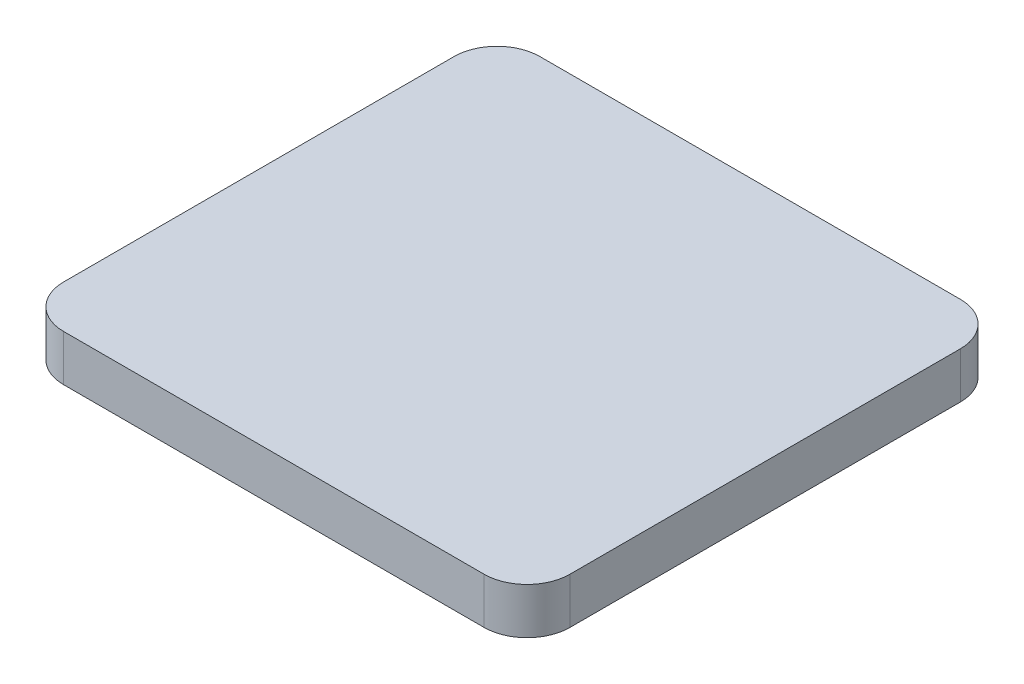
SolidWorks part; units mm, degrees
ref_plane "Front Plane" through (0, 0, 0) normal (0, 0, 1) x (1, 0, 0)
ref_plane "Top Plane" through (0, 0, 0) normal (0, 1, 0) x (1, 0, 0)
ref_plane "Right Plane" through (0, 0, 0) normal (1, 0, 0) x (0, 0, -1)
sketch "Sketch1" plane through (0, 0, 0) normal (0, 1, 0) x (1, 0, 0)
  line L0 (-21.6, 20.2) -> (-21.6, 22.2) construction
  line L1 (19.6, 20.2) -> (-19.6, 20.2)
  line L2 (21.6, 18.2) -> (21.6, -18.2)
  line L3 (19.6, -20.2) -> (-19.6, -20.2)
  line L4 (-21.6, 18.2) -> (-21.6, -18.2)
  line L5 (21.6, 20.2) -> (-21.6, -20.2) construction
  line L6 (21.6, -20.2) -> (-21.6, 20.2) construction
  line L7 (23.6, -22.2) -> (-23.6, -22.2)
  line L8 (23.6, -22.2) -> (23.6, 22.2)
  line L9 (23.6, 22.2) -> (-23.6, 22.2)
  line L10 (-23.6, -22.2) -> (-23.6, 22.2)
  line L11 (23.6, -22.2) -> (-23.6, 22.2) construction
  line L12 (23.6, 22.2) -> (-23.6, -22.2) construction
  line L13 (-21.6, 20.2) -> (-23.6, 20.2) construction
  arc A0 (-19.6, -20.2) -> (-21.6, -18.2) centre (-19.6, -18.2) cw
  arc A1 (21.6, -18.2) -> (19.6, -20.2) centre (19.6, -18.2) cw
  arc A2 (19.6, 20.2) -> (21.6, 18.2) centre (19.6, 18.2) cw
  arc A3 (-19.6, 20.2) -> (-21.6, 18.2) centre (-19.6, 18.2) ccw
  circle A4 centre (-19.6, 18.2) radius 4
  circle A5 centre (19.6, 18.2) radius 4
  circle A6 centre (19.6, -18.2) radius 4
  circle A7 centre (-19.6, -18.2) radius 4
  point P0 (0, 0)
  point P6 (0, 0)
  dimension "D4" = 2
  dimension "D1" = 43.2
  dimension "D2" = 40.4
  dimension "D3" = 2
extrude "Boss-Extrude1" add sketch "Sketch1" along normal blind 1.3 contours L1 A4 L4 A3 | A7 L4 A4 L10 | A7 L3 A0 L4 | A7 L7 A6 L3 | A6 L2 A1 L3 | A6 L8 A5 L2 | L2 A5 L1 A2 | A5 L9 A4 L1 region at (17.8679, 0, -20.3056) region at (0, 0, -21.2258) region at (-17.8679, 0, -20.3056) region at (22.6281, 0, 0) region at (22.9727, 0, 16.2528) region at (-22.6281, 0, 0) region at (0, 0, 21.2258) region at (-21.7056, 0, 16.4679)
sketch "Sketch2" plane through (0, 1.3, 0) normal (0, 1, 0) x (1, 0, 0)
  line L4 (-19.6, -22.2) -> (19.6, -22.2)
  line L5 (23.6, -18.2) -> (23.6, 18.2)
  line L6 (19.6, 22.2) -> (-19.6, 22.2)
  line L7 (-23.6, 18.2) -> (-23.6, -18.2)
  line L8 (-19.6, -22.2) -> (19.6, -22.2)
  line L9 (23.6, -18.2) -> (23.6, 18.2)
  line L10 (19.6, 22.2) -> (-19.6, 22.2)
  line L11 (-23.6, 18.2) -> (-23.6, -18.2)
  arc A4 (19.6, -22.2) -> (23.6, -18.2) centre (19.6, -18.2) ccw
  arc A5 (23.6, 18.2) -> (19.6, 22.2) centre (19.6, 18.2) ccw
  arc A6 (-19.6, 22.2) -> (-23.6, 18.2) centre (-19.6, 18.2) ccw
  arc A7 (-23.6, -18.2) -> (-19.6, -22.2) centre (-19.6, -18.2) ccw
  arc A8 (19.6, -22.2) -> (23.6, -18.2) centre (19.6, -18.2) ccw
  arc A9 (23.6, 18.2) -> (19.6, 22.2) centre (19.6, 18.2) ccw
  arc A10 (-19.6, 22.2) -> (-23.6, 18.2) centre (-19.6, 18.2) ccw
  arc A11 (-23.6, -18.2) -> (-19.6, -22.2) centre (-19.6, -18.2) ccw
  dimension "D1" = 0
extrude "Boss-Extrude2" add sketch "Sketch2" along normal blind 1
sketch "Sketch3" plane through (0, 1.3, 0) normal (0, -1, 0) x (1, 0, 0)
  line L0 (-23.6, 0) -> (23.6, 0) construction
  line L1 (-23.6, 18.2) -> (-23.6, -18.2) construction
  line L2 (23.6, 18.2) -> (23.6, -18.2) construction
  line L3 (-23.6, 11.1) -> (23.6, 11.1) construction
  line L4 (0, 11.1) -> (0, 22.2) construction
  line L5 (19.6, 22.2) -> (-19.6, 22.2) construction
  line L6 (0, 11.1) -> (0, 0) construction
  line L7 (-23.6, -11.1) -> (23.6, -11.1) construction
  line L8 (0, 0) -> (4.1348, 4.1348) construction
  line L9 (11.1, -23.6) -> (11.1, 23.6) construction
  line L10 (-11.1, -23.6) -> (-11.1, 23.6) construction
  line L11 (-21.6, -18.2) -> (-21.6, 18.2) construction
  line L12 (-21.6, -18.2) -> (-21.6, 18.2) construction
  line L13 (19.6, -20.2) -> (-19.6, -20.2) construction
  line L14 (21.6, -18.2) -> (21.6, 18.2) construction
  line L15 (19.6, 20.2) -> (-19.6, 20.2) construction
  line L16 (19.6, 20.2) -> (-19.6, 20.2) construction
  circle A0 centre (-21.6, 11.1) radius 0.4
  circle A1 centre (-21.6, 0) radius 0.4
  circle A2 centre (-21.6, -11.1) radius 0.4
  circle A3 centre (-11.1, -20.2) radius 0.4
  circle A4 centre (11.1, -20.2) radius 0.4
  circle A5 centre (21.6, -11.1) radius 0.4
  circle A6 centre (21.6, 0) radius 0.4
  circle A7 centre (21.6, 11.1) radius 0.4
  circle A8 centre (11.1, 20.2) radius 0.4
  circle A9 centre (0, 20.2) radius 0.4
  circle A10 centre (-11.1, 20.2) radius 0.4
  point P56 (-21.6, 0)
  point P57 (21.6, -10.85)
  dimension "D2" = 0.8
  dimension "D1" = 45
extrude "Boss-Extrude3" add sketch "Sketch3" along normal up to surface (1.3 mm away) up to face at (0, 0, 0)
sketch "Sketch4" plane through (0, 0, 0) normal (0, -1, 0) x (1, 0, 0)
  line L0 (-22.6, 18.2) -> (-22.6, -18.2)
  line L1 (-19.6, -21.2) -> (19.6, -21.2)
  line L2 (22.6, -18.2) -> (22.6, 18.2)
  line L3 (19.6, 21.2) -> (-19.6, 21.2)
  line L4 (19.6, 22.2) -> (-19.6, 22.2)
  line L5 (-23.6, 18.2) -> (-23.6, -18.2)
  line L6 (-19.6, -22.2) -> (19.6, -22.2)
  line L7 (23.6, -18.2) -> (23.6, 18.2)
  line L8 (19.6, 22.2) -> (-19.6, 22.2)
  line L9 (-23.6, 18.2) -> (-23.6, -18.2)
  line L10 (-19.6, -22.2) -> (19.6, -22.2)
  line L11 (23.6, -18.2) -> (23.6, 18.2)
  arc A0 (-19.6, 21.2) -> (-22.6, 18.2) centre (-19.6, 18.2) ccw
  arc A1 (-22.6, -18.2) -> (-19.6, -21.2) centre (-19.6, -18.2) ccw
  arc A2 (19.6, -21.2) -> (22.6, -18.2) centre (19.6, -18.2) ccw
  arc A3 (22.6, 18.2) -> (19.6, 21.2) centre (19.6, 18.2) ccw
  arc A4 (-19.6, 22.2) -> (-23.6, 18.2) centre (-19.6, 18.2) ccw
  arc A5 (-23.6, -18.2) -> (-19.6, -22.2) centre (-19.6, -18.2) ccw
  arc A6 (19.6, -22.2) -> (23.6, -18.2) centre (19.6, -18.2) ccw
  arc A7 (23.6, 18.2) -> (19.6, 22.2) centre (19.6, 18.2) ccw
  arc A8 (-19.6, 22.2) -> (-23.6, 18.2) centre (-19.6, 18.2) ccw
  arc A9 (-23.6, -18.2) -> (-19.6, -22.2) centre (-19.6, -18.2) ccw
  arc A10 (19.6, -22.2) -> (23.6, -18.2) centre (19.6, -18.2) ccw
  arc A11 (23.6, 18.2) -> (19.6, 22.2) centre (19.6, 18.2) ccw
  dimension "D1" = 0
  dimension "D2" = 1
extrude "Boss-Extrude4" add sketch "Sketch4" along normal blind 2
